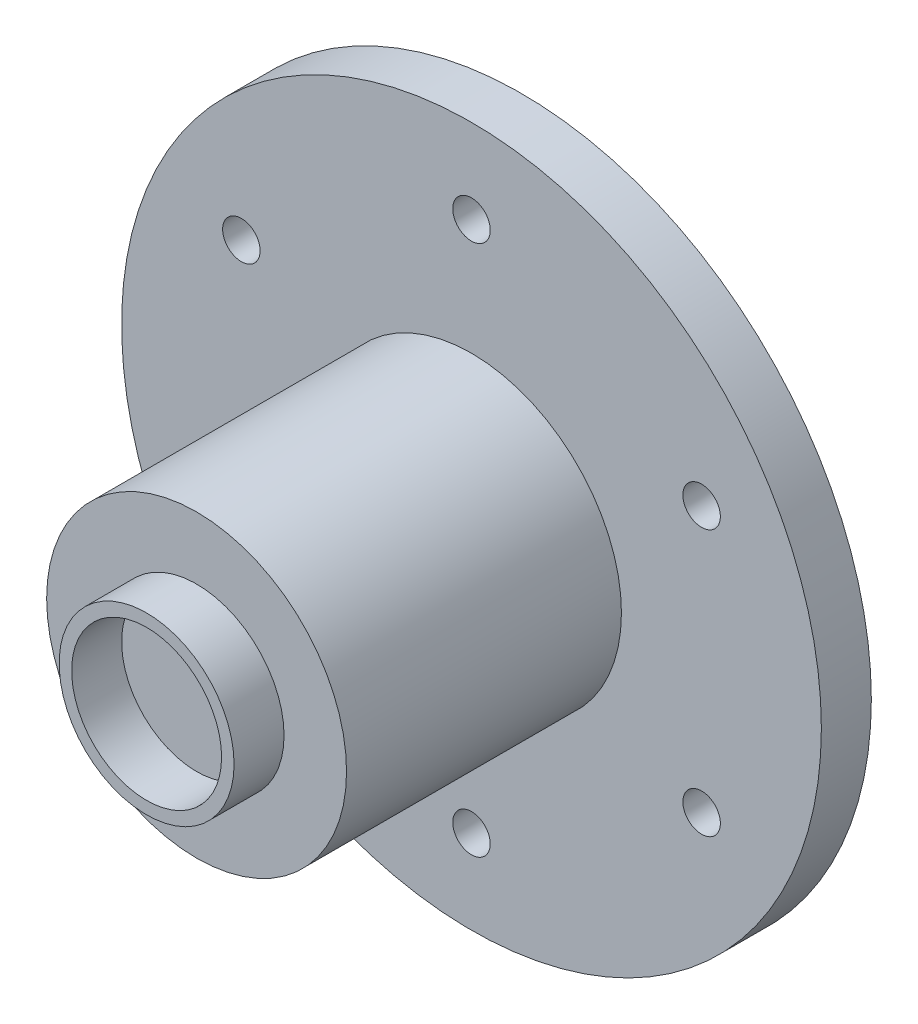
SolidWorks part; units mm, degrees
ref_plane "前视基准面" through (0, 0, 0) normal (0, 0, 1) x (1, 0, 0)
ref_plane "上视基准面" through (0, 0, 0) normal (0, 1, 0) x (1, 0, 0)
ref_plane "右视基准面" through (0, 0, 0) normal (1, 0, 0) x (0, 0, -1)
sketch "草图1" plane through (0, 0, 0) normal (0, 0, 1) x (1, 0, 0)
  circle A0 centre (0, 0) radius 28
  dimension "D1" = 56
extrude "凸台-拉伸1" add sketch "草图1" along normal blind 4 contours A0
sketch "草图2" plane through (0, 0, 4) normal (0, 0, 1) x (1, 0, 0)
  circle A0 centre (0, 0) radius 12
  dimension "D1" = 24
extrude "凸台-拉伸2" add sketch "草图2" along normal blind 22 contours A0
sketch "草图3" plane through (0, 0, 26) normal (0, 0, 1) x (1, 0, 0)
  circle A0 centre (0, 0) radius 5
  dimension "D1" = 10
extrude "切除-拉伸1" cut sketch "草图3" against normal blind 60 contours A0
sketch "草图4" plane through (0, 0, 0) normal (0, 0, -1) x (-1, 0, 0)
  circle A0 centre (0, 21.2656) radius 1.5
  dimension "D1" = 3
extrude "切除-拉伸2" cut sketch "草图4" against normal blind 7 contours A0
ref_axis "基准轴1" through (0, 0, -1.3) along (0, 0, 1)
pattern_circular "阵列(圆周)1" count 6 every 60 about axis through (0, 0, -1.3) along (0, 0, 1) of "切除-拉伸2"
sketch "草图5" plane through (0, 0, 0) normal (0, 1, 0) x (1, 0, 0)
  line L0 (0, 1.3) -> (0, -27.3) construction
  circle A0 centre (0, -16.2233) radius 1.5
  dimension "D1" = 3
extrude "切除-拉伸3" cut sketch "草图5" against normal blind 15 contours A0
ref_plane "基准面1" through (0, 0, 20) normal (0, 0, 1) x (1, 0, 0)
sketch "草图7" plane through (0, 0, 20) normal (0, 0, 1) x (1, 0, 0)
  circle A0 centre (0, 0) radius 7
  dimension "D1" = 14
extrude "凸台-拉伸4" add sketch "草图7" along normal blind 10 contours A0
sketch "草图8" plane through (0, 0, 30) normal (0, 0, 1) x (1, 0, 0)
  circle A0 centre (0, 0) radius 6
  dimension "D1" = 12
extrude "切除-拉伸4" cut sketch "草图8" against normal blind 4 contours A0
